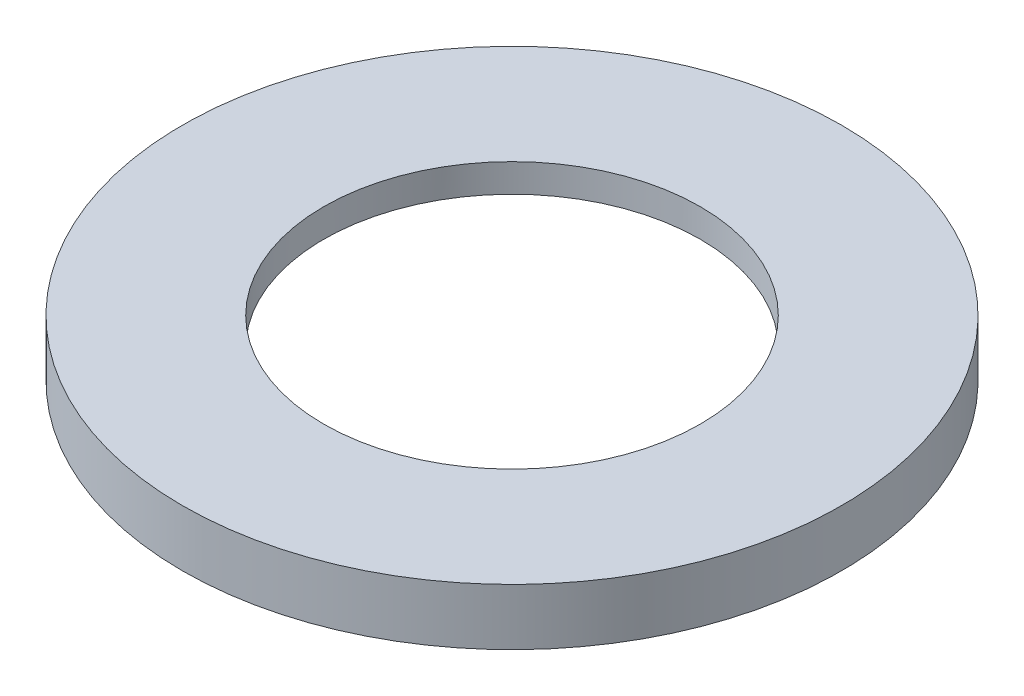
SolidWorks part; units mm, degrees
ref_plane "Front Plane" through (0, 0, 0) normal (0, 0, 1) x (1, 0, 0)
ref_plane "Top Plane" through (0, 0, 0) normal (0, 1, 0) x (1, 0, 0)
ref_plane "Right Plane" through (0, 0, 0) normal (1, 0, 0) x (0, 0, -1)
sketch "Sketch1" plane through (0, 0, 0) normal (0, 1, 0) x (1, 0, 0)
  circle A0 centre (0, 0) radius 35
  circle A1 centre (0, 0) radius 20
  dimension "D1" = 70
  dimension "D2" = 40
extrude "Boss-Extrude1" add sketch "Sketch1" along normal blind 6
sketch "Sketch2" plane through (0, 0, 0) normal (1, 0, 0) x (0, 0, -1)
  line L0 (-35, 0) -> (35, 0) construction
  line L1 (-20, 0) -> (-27.5, 0)
  line L2 (-20, 0) -> (-20, 3)
  line L3 (-20, 3) -> (-27.5, 3)
  line L4 (-27.5, 0) -> (-27.5, 3)
  line L5 (-20, 0) -> (20, 0) construction
  line L6 (-20, 0) -> (20, 0) construction
  line L7 (0, 0) -> (0, 13.052) construction
  dimension "D1" = 7.5
  dimension "D2" = 3
revolve "Cut-Revolve1" cut sketch "Sketch2" angle 360 about L7
